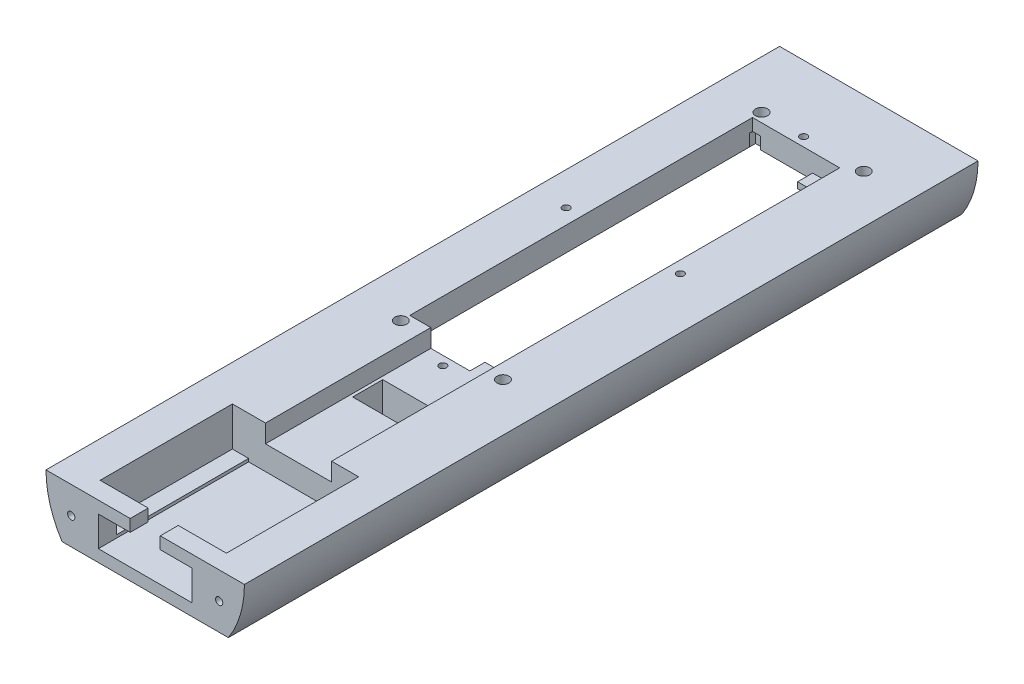
SolidWorks part; units mm, degrees
ref_plane "前视基准面" through (0, 0, 0) normal (0, 0, 1) x (1, 0, 0)
ref_plane "上视基准面" through (0, 0, 0) normal (0, 1, 0) x (1, 0, 0)
ref_plane "右视基准面" through (0, 0, 0) normal (1, 0, 0) x (0, 0, -1)
other "Configuration Table"
sketch "草图1" plane through (0, 0, 0) normal (0, 1, 0) x (1, 0, 0)
  line L1 (0, 0) -> (33, 0)
  line L2 (0, 0) -> (0, -122)
  line L3 (0, -122) -> (33, -122)
  line L4 (33, 0) -> (33, -122)
  dimension "D1" = 33
  dimension "D2" = 122
extrude "凸台-拉伸1" add sketch "草图1" along normal blind 9
sketch "草图2" plane through (0, 0, 0) normal (0, -1, 0) x (1, 0, 0)
  line L0 (0, 0) -> (0, 122) construction
  line L1 (8, 67) -> (22, 67)
  line L2 (8, 67) -> (8, 15)
  line L3 (8, 15) -> (22, 15)
  line L4 (22, 67) -> (22, 15)
  line L5 (33, 122) -> (33, 0) construction
  line L6 (33, 0) -> (0, 0) construction
  line L7 (0, 122) -> (33, 122) construction
  line L8 (6, 119) -> (27, 119)
  line L9 (6, 119) -> (6, 97)
  line L10 (6, 97) -> (27, 97)
  line L11 (27, 119) -> (27, 97)
  dimension "D1" = 52
  dimension "D2" = 8
  dimension "D3" = 11
  dimension "D4" = 15
  dimension "D5" = 6
  dimension "D6" = 6
  dimension "D7" = 3
  dimension "D8" = 22
extrude "切除-拉伸1" cut sketch "草图2" against normal through all
extrude "凸台-拉伸2" add sketch "草图2<2>" against normal blind 2.5 contours L10 L11 L8 L9
sketch "草图2<2>" plane through (0, 0, 0) normal (0, -1, 0) x (1, 0, 0) same geometry as "草图2"
sketch "草图3" plane through (0, 0, 0) normal (0, -1, 0) x (1, 0, 0)
  line L0 (8, 67) -> (8, 15) construction
  line L1 (3, 75) -> (27, 75)
  line L2 (3, 75) -> (3, 7)
  line L3 (3, 7) -> (27, 7)
  line L4 (27, 75) -> (27, 7)
  line L5 (22, 15) -> (22, 67) construction
  line L6 (8, 15) -> (22, 15) construction
  line L7 (22, 67) -> (8, 67) construction
  dimension "D1" = 5
  dimension "D2" = 5
  dimension "D3" = 8
  dimension "D4" = 8
extrude "切除-拉伸2" cut sketch "草图3" against normal blind 5
sketch "草图4" plane through (0, 5, 0) normal (0, -1, 0) x (1, 0, 0)
  line L0 (8, 71) -> (25, 71) construction
  line L2 (8, 75) -> (8, 67) construction
  line L3 (27, 75) -> (3, 75) construction
  line L4 (8, 67) -> (22, 67) construction
  line L5 (16.5, 71) -> (16.5, 0) construction
  line L7 (33, 0) -> (0, 0) construction
  line L8 (27, 7) -> (27, 75) construction
  line L9 (8, 15) -> (8, 7) construction
  line L10 (22, 15) -> (8, 15) construction
  line L11 (3, 7) -> (27, 7) construction
  circle A0 centre (25, 71) radius 1
  circle A1 centre (8, 71) radius 1
  circle A2 centre (8, 71) radius 2
  circle A3 centre (25, 71) radius 2
  circle A4 centre (25, 11) radius 2
  circle A5 centre (25, 11) radius 1
  circle A6 centre (8, 11) radius 2
  circle A7 centre (8, 11) radius 1
  dimension "D1" = 4
  dimension "D2" = 2
extrude "切除-拉伸3" cut sketch "草图4" against normal through all contours A1 | A0 | A5 | A7
extrude "切除-拉伸4" cut sketch "草图4<3>" against normal blind 2 contours A2 | A3 | A4 | A6
sketch "草图4<3>" plane through (0, 5, 0) normal (0, -1, 0) x (1, 0, 0) same geometry as "草图4"
sketch "草图5" plane through (0, 5, 0) normal (0, -1, 0) x (1, 0, 0)
  line L0 (15, 75) -> (15, 67) construction
  line L1 (27, 75) -> (3, 75) construction
  line L2 (8, 67) -> (22, 67) construction
  line L3 (15, 15) -> (15, 7) construction
  line L6 (3, 41) -> (8, 41) construction
  line L7 (3, 75) -> (3, 7) construction
  line L8 (8, 15) -> (8, 67) construction
  line L9 (27, 41) -> (22, 41) construction
  line L10 (27, 7) -> (27, 75) construction
  line L11 (22, 67) -> (22, 15) construction
  line L12 (22, 15) -> (8, 15) construction
  line L13 (3, 7) -> (27, 7) construction
  circle A0 centre (15, 71) radius 0.6
  circle A1 centre (5.5, 41) radius 0.6
  circle A2 centre (24.5, 41) radius 0.6
  circle A3 centre (15, 11) radius 0.6
  dimension "D1" = 1.2
extrude "切除-拉伸5" cut sketch "草图5" against normal through all
sketch "草图6" plane through (0, 0, 122) normal (0, 0, 1) x (1, 0, 0)
  line L0 (0, 9) -> (33, 9) construction
  circle A0 centre (16.5, 9) radius 16.5
  dimension "D1" = 33
extrude "切除-拉伸6" cut sketch "草图6" against normal through all flip side to cut
sketch "草图7" plane through (0, 0, 122) normal (0, 0, 1) x (1, 0, 0)
  line L0 (8.7, 7) -> (0, 9) construction
  line L1 (8.7, 7) -> (24.3, 7)
  line L2 (8.7, 7) -> (8.7, 2)
  line L3 (8.7, 2) -> (24.3, 2)
  line L4 (24.3, 7) -> (24.3, 2)
  line L5 (0, 9) -> (33, 9) construction
  line L6 (24.3, 7) -> (33, 9) construction
  line L7 (16.5, 9) -> (16.5, 7) construction
  line L8 (4.2, 4.5) -> (8.7, 4.5) construction
  line L9 (24.3, 4.5) -> (28.8, 4.5) construction
  line L10 (14, 9) -> (19, 9)
  line L11 (14, 9) -> (14, 7)
  line L12 (14, 7) -> (19, 7)
  line L13 (19, 9) -> (19, 7)
  arc A0 (30.3293, 0) -> (33, 9) centre (16.5, 9) ccw construction
  circle A1 centre (4.2, 4.5) radius 0.6
  circle A2 centre (28.8, 4.5) radius 0.6
  dimension "D4" = 1.2
  dimension "D1" = 8.7
  dimension "D2" = 7
  dimension "D3" = 2
  dimension "D5" = 4.5
  dimension "D6" = 5
extrude "切除-拉伸7" cut sketch "草图7" against normal up to surface (25 mm away) contours L1 L4 L3 L2 | L13 L12 L11 L10 up to face at (16.5, 5.75, 97)
extrude "切除-拉伸8" cut sketch "草图7<3>" against normal blind 3 contours A1 | A2
sketch "草图7<3>" plane through (0, 0, 122) normal (0, 0, 1) x (1, 0, 0) same geometry as "草图7"
sketch "草图8" plane through (0, 5, 0) normal (0, -1, 0) x (1, 0, 0)
  line L0 (8, 67) -> (22, 67) construction
  line L1 (8, 69.5) -> (18, 69.5)
  line L2 (8, 69.5) -> (8, 12.5)
  line L3 (8, 12.5) -> (18, 12.5)
  line L4 (18, 69.5) -> (18, 12.5)
  line L5 (22, 15) -> (8, 15) construction
  line L7 (8, 15) -> (8, 67) construction
  dimension "D1" = 10
  dimension "D2" = 2.5
  dimension "D3" = 2.5
extrude "切除-拉伸11" cut sketch "草图8" against normal through all
sketch "草图9" plane through (0, 0, 0) normal (0, -1, 0) x (1, 0, 0)
  line L0 (16.5, 78) -> (16.5, 0) construction
  line L1 (12, 83) -> (21, 83)
  line L2 (12, 83) -> (12, 78)
  line L3 (12, 78) -> (21, 78)
  line L4 (21, 83) -> (21, 78)
  line L5 (30.3293, 0) -> (2.6707, 0) construction
  line L6 (27, 75) -> (3, 75) construction
  dimension "D1" = 9
  dimension "D2" = 5
  dimension "D3" = 3
extrude "切除-拉伸12" cut sketch "草图9" against normal through all
sketch "草图10" plane through (0, 9, 0) normal (0, 1, 0) x (1, 0, 0)
  line L0 (12, -83) -> (12, -78) construction
  line L1 (12, -83) -> (21, -83)
  line L2 (12, -83) -> (12, -97)
  line L3 (12, -97) -> (21, -97)
  line L4 (21, -83) -> (21, -97)
  line L5 (21, -83) -> (12, -83) construction
  line L6 (6, -97) -> (27, -97) construction
  line L7 (21, -78) -> (21, -83) construction
  line L9 (17, -67) -> (21, -67)
  line L10 (17, -67) -> (17, -78)
  line L11 (17, -78) -> (21, -78)
  line L12 (21, -67) -> (21, -78)
  line L13 (12, -78) -> (21, -78) construction
  line L14 (22, -67) -> (18, -67) construction
  dimension "D1" = 4
extrude "切除-拉伸13" cut sketch "草图10" against normal blind 3
sketch "草图11" plane through (0, 9, 0) normal (0, 1, 0) x (1, 0, 0)
  line L13 (11.5, -12.5) -> (22.5, -12.5)
  line L14 (11.5, -12.5) -> (11.5, -97)
  line L15 (11.5, -97) -> (22.5, -97)
  line L16 (22.5, -12.5) -> (22.5, -97)
  line L17 (21, -97) -> (27, -97) construction
  line L18 (16.5, 0) -> (17, -12.5) construction
  line L19 (33, 0) -> (0, 0) construction
  line L20 (17, -69.5) -> (17, -78) construction
  line L22 (8, -12.5) -> (18, -12.5) construction
  point P14 (0, 0)
  dimension "D1" = 11
extrude "切除-拉伸14" cut sketch "草图11" against normal up to surface (3 mm away) up to face at (16.5, 6, 90)
